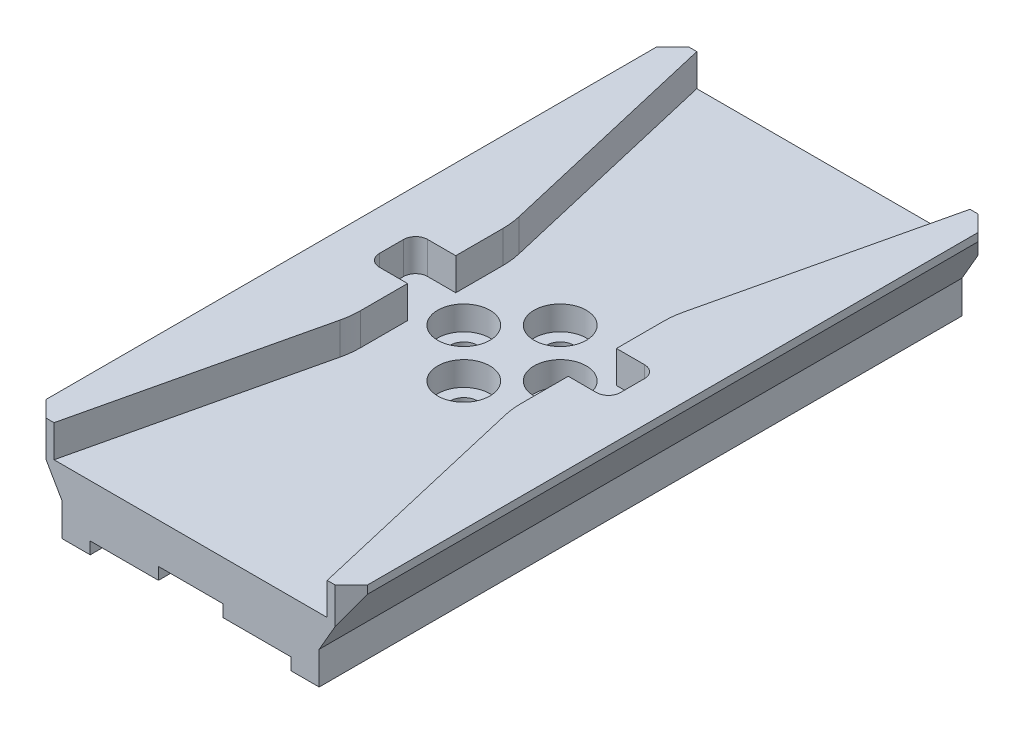
SolidWorks part; units mm, degrees
material "Сплав 2024"
ref_plane "Спереди" through (0, 0, 0) normal (0, 0, 1) x (1, 0, 0)
ref_plane "Сверху" through (0, 0, 0) normal (0, 1, 0) x (1, 0, 0)
ref_plane "Справа" through (0, 0, 0) normal (1, 0, 0) x (0, 0, -1)
sketch "Эскиз1" plane through (0, 0, 0) normal (0, 0, 1) x (1, 0, 0)
  line L0 (-20, 5) -> (-16, -1.9282)
  line L1 (-20, 6) -> (20, 6)
  line L2 (-25.6942, 6) -> (28.5829, 6) construction
  line L3 (-16, -6) -> (16, -6)
  line L4 (0, 6) -> (0, -6) construction
  line L5 (-22.304, 8.9907) -> (-15.6808, -2.4811) construction
  line L7 (-16, -1.9282) -> (-16, -6)
  line L9 (-20, 6) -> (-20, 5)
  line L10 (16, -1.9282) -> (16, -6)
  line L11 (20, 5) -> (16, -1.9282)
  line L12 (20, 6) -> (20, 5)
  point P15 (-20.5774, 6)
  dimension "D1" = 16
  dimension "D2" = 12
  dimension "D3" = 60
  dimension "D4" = 20.5774
  dimension "D6" = 20
  dimension "D7" = 1
extrude "Бобышка-Вытянуть1" add sketch "Эскиз1" along normal blind 80
sketch "Эскиз2" plane through (0, 6, 0) normal (0, 1, 0) x (1, 0, 0)
  line L0 (0, 0) -> (0, -80) construction
  line L1 (20, 0) -> (-20, 0) construction
  line L2 (20, -80) -> (-20, -80) construction
  line L3 (-17, 0) -> (-17, -80) construction
  line L4 (10, -50) -> (17, -80)
  line L5 (-17, 0) -> (-10, -30)
  line L6 (-10, -30) -> (-10, -50)
  line L7 (-10, -50) -> (-17, -80)
  line L8 (10, -30) -> (10, -50)
  line L9 (17, 0) -> (10, -30)
  line L10 (20, -40) -> (-20, -40) construction
  line L11 (-17, 0) -> (17, 0)
  line L12 (17, -80) -> (-17, -80)
  line L20 (-20, -80) -> (-20, 0) construction
  line L21 (20, -80) -> (20, 0) construction
  point P24 (-10, -40)
  dimension "D1" = 10
  dimension "D2" = 3
  dimension "D3" = 20
extrude "Вырез-Вытянуть1" cut sketch "Эскиз2" against normal blind 4
sketch "Эскиз3" plane through (0, 6, 0) normal (0, 1, 0) x (1, 0, 0)
  line L0 (20, -40) -> (-20, -40) construction
  line L4 (-10, -37) -> (-15, -37)
  line L5 (-10, -37) -> (-10, -43)
  line L6 (-10, -43) -> (-15, -43)
  line L7 (-15, -37) -> (-15, -43)
  line L8 (0, 0) -> (0, -80) construction
  line L9 (17, 0) -> (-17, 0) construction
  line L10 (-17, -80) -> (17, -80) construction
  line L11 (10, -37) -> (10, -43)
  line L12 (10, -43) -> (15, -43)
  line L13 (15, -37) -> (15, -43)
  line L14 (10, -37) -> (15, -37)
  line L15 (-10, -30) -> (-10, -50) construction
  line L16 (20, -80) -> (20, 0) construction
  line L17 (-20, -80) -> (-20, 0) construction
  point P12 (-10, -40)
  dimension "D1" = 6
  dimension "D2" = 5
extrude "Вырез-Вытянуть2" cut sketch "Эскиз3" against normal blind 4
fillet "Скругление1" [suppressed] radius 1.5
fillet "Скругление2" radius 10 4 edges at (10, 4, 50) (10, 4, 30) (-10, 4, 30) (-10, 4, 50)
sketch "Эскиз4" plane through (0, 2, 0) normal (0, 1, 0) x (1, 0, 0)
  line L0 (0, 0) -> (0, -80) construction
  line L1 (-17, -80) -> (17, -80) construction
  line L2 (20, -40) -> (-20, -40) construction
  line L5 (20, -80) -> (20, 0) construction
  line L6 (-20, -80) -> (-20, 0) construction
  circle A0 centre (0, -40) radius 6 construction
  dimension "D1" = 12
hole_wizard "Цековка для винта с внутренним шестигранником M31" positions "Эскиз6" profile "Эскиз5" counterbore size "M3" standard "Ansi Metric" end condition through all
sketch "Эскиз6" plane through (0, 2, 0) normal (0, 1, 0) x (1, 0, 0)
  line L0 (0, 0) -> (0, -80) construction
  line L1 (20, -40) -> (-20, -40) construction
  circle A0 centre (0, -40) radius 6 construction
  point P0 (0, -34)
  point P2 (6, -40)
  point P4 (0, -46)
  point P6 (-6, -40)
sketch "Эскиз5" plane through (0, 2, 34) normal (1, 0, 0) x (0, 0, 1)
  line L0 (0, 0) -> (0, 8)
  line L1 (0, 8) -> (1.7, 8)
  line L3 (1.7, 8) -> (1.7, 3)
  line L4 (1.7, 3) -> (3.25, 3)
  line L5 (3.25, 3) -> (3.25, 0)
  line L7 (3.25, 0) -> (0, 0)
  line L11 (0, -6.35) -> (0, 107.95) construction
  dimension "Диаметр сквозного отверстия" = 3.4
  dimension "Глубина сквозного отверстия" = 8
  dimension "Диаметр цековки" = 6.5
  dimension "Глубина цековки" = 3
sketch "Эскиз7" plane through (0, -6, 0) normal (0, -1, 0) x (1, 0, 0)
  line L0 (0, 80) -> (0, 0) construction
  line L2 (-11.5, 77) -> (11.5, 77)
  line L3 (-11.5, 77) -> (-11.5, 51)
  line L5 (-16, 80) -> (16, 80) construction
  line L6 (11.5, 77) -> (11.5, 51)
  line L7 (-11.5, 77) -> (11.5, 51) construction
  line L8 (-11.5, 51) -> (11.5, 77) construction
  arc A0 (-11.5, 51) -> (11.5, 51) centre (0, 19) cw
  point P0 (0, 64)
  dimension "D2" = 26
  dimension "D5" = 45
  dimension "D1" = 3
  dimension "D3" = 23
  dimension "D4" = 26
extrude "Вырез-Вытянуть3" cut sketch "Эскиз7" against normal blind 7
sketch "Эскиз8" plane through (0, 1, 0) normal (0, -1, 0) x (1, 0, 0)
  line L0 (0, 80) -> (0, 0) construction
  line L1 (-16, 80) -> (16, 80) construction
  line L2 (-16, 61.2) -> (16, 61.2) construction
  line L3 (-16, 80) -> (-16, 0) construction
  line L4 (16, 80) -> (16, 0) construction
  line L6 (13.1, 58.95) -> (7.1, 63.45) construction
  line L7 (-13.1, 63.45) -> (-7.1, 63.45)
  line L8 (-13.1, 63.45) -> (-13.1, 58.95)
  line L9 (-13.1, 58.95) -> (-7.1, 58.95)
  line L10 (13.1, 63.45) -> (7.1, 58.95) construction
  line L11 (-13.1, 63.45) -> (-7.1, 58.95) construction
  line L12 (-13.1, 58.95) -> (-7.1, 63.45) construction
  line L13 (13.1, 58.95) -> (7.1, 58.95)
  line L14 (13.1, 63.45) -> (13.1, 58.95)
  line L15 (13.1, 63.45) -> (7.1, 63.45)
  arc A0 (-7.1, 58.95) -> (-7.1, 63.45) centre (-7.1, 61.2) ccw
  arc A1 (7.1, 58.95) -> (7.1, 63.45) centre (7.1, 61.2) cw
  point P17 (-10.1, 61.2)
  point P24 (10.1, 61.2)
  dimension "D1" = 7.1
  dimension "D2" = 4.5
  dimension "D3" = 10.2
  dimension "D4" = 3
extrude "Бобышка-Вытянуть2" add sketch "Эскиз8" along normal blind 3
hole_wizard "Отверстие обработанное метчиком M2.5x0.451" positions "Эскиз10" profile "Эскиз9" tap size "M2.5x0.45" standard "Ansi Metric"
sketch "Эскиз10" plane through (0, -2, 0) normal (0, -1, 0) x (-1, 0, 0)
  point P0 (7.1, -61.2)
  point P2 (-7.1, -61.2)
sketch "Эскиз9" plane through (-7.1, -2, 61.2) normal (1, 0, 0) x (0, 0, -1)
  line L0 (0, 0) -> (0, 3.6159)
  line L1 (0, 3.6159) -> (1.025, 3)
  line L2 (1.025, 3) -> (1.025, 0)
  line L5 (1.025, 0) -> (0, 0)
  line L10 (0, 3.6159) -> (-1.025, 3) construction
  line L11 (0, -6.35) -> (0, 107.95) construction
  dimension "Диаметр сверла" = 2.05
  dimension "Глубина сверла" = 3
  dimension "Угол заточки сверла" = 118
cosmetic thread "Отверстие резьбы7" parameters "D1"=3, "D2"=2.5
cosmetic thread "Отверстие резьбы8" parameters "D1"=3, "D2"=2.5
sketch "Эскиз12" plane through (0, 1, 0) normal (0, -1, 0) x (1, 0, 0)
  line L0 (0, 77) -> (0, 51) construction
  line L1 (11.5, 77) -> (-11.5, 77) construction
  line L2 (-11.5, 51) -> (11.5, 51) construction
  line L3 (-1.8247, 64) -> (1.8247, 64) construction
  line L4 (-13.6614, 76) -> (7.1704, 76) construction
  line L5 (-11.5, 80.8402) -> (-11.5, 69.1924) construction
  line L6 (-11.5, 77) -> (-11.5, 51) construction
  circle A0 centre (-11.5, 76) radius 2
  circle A3 centre (11.5, 76) radius 2
  circle A4 centre (11.5, 52) radius 2
  circle A6 centre (-11.5, 52) radius 2
  point P14 (0, 64)
  dimension "D3" = 4
  dimension "D2" = 1
sketch "Эскиз15" plane through (0, 1, 0) normal (0, -1, 0) x (1, 0, 0)
  line L0 (0, 77) -> (0, 51) construction
  line L1 (11.5, 77) -> (-11.5, 77) construction
  line L2 (-13.8501, 64) -> (13.8501, 64) construction
  line L4 (-11.5, 51) -> (11.5, 51) construction
  line L5 (11.5, 51) -> (11.5, 77) construction
  line L7 (11.5, 77) -> (-11.5, 77) construction
  line L8 (-11.5, 77) -> (-11.5, 63.45) construction
  line L9 (-11.5, 77) -> (-11.5, 51) construction
  circle A0 centre (-11.5, 51) radius 2.5
  circle A1 centre (11.5, 51) radius 2.5
  circle A2 centre (-9, 77) radius 2.5
  circle A3 centre (9, 77) radius 2.5
  point P8 (0, 64)
  dimension "D1" = 5
  dimension "D2" = 5
  dimension "D3" = 5
extrude "Бобышка-Вытянуть5" add sketch "Эскиз15" along normal up to surface (7 mm away) up to face at (0, -6, 64.5009)
fillet "Скругление8" radius 3 12 edges at (11.5, -2.5, 53.5) (9.1178, -2.5, 51.7584) (-9.1178, -2.5, 51.7584) (-11.5, -2.5, 53.5) (-11.5, -0.5, 58.95) (11.5, -0.5, 58.95) (11.5, -0.5, 63.45) (-11.5, -0.5, 63.45) (-11.5, -2.5, 77) (11.5, -2.5, 77) (6.5, -2.5, 77) (-6.5, -2.5, 77)
sketch "Эскиз16" plane through (0, -6, 0) normal (0, -1, 0) x (1, 0, 0)
  line L0 (-16, 80) -> (16, 80) construction
  line L1 (-12.5, 80) -> (12.5, 80)
  line L70 (-12.5, 54.3541) -> (-12.5, 80)
  line L71 (12.5, 54.3541) -> (12.5, 80)
  line L72 (-11.5, 71.5228) -> (-11.5, 55.6098) construction
  line L73 (11.5, 55.6098) -> (11.5, 71.5228) construction
  arc A0 (7.2531, 52.2211) -> (-7.2531, 52.2211) centre (0, 19) ccw construction
  arc A1 (7.2531, 52.2211) -> (-7.2531, 52.2211) centre (0, 19) ccw construction
  arc A2 (8.0001, 51.0194) -> (-8.0001, 51.0194) centre (0, 19) ccw
  arc A3 (7.0398, 51.2441) -> (-7.0398, 51.2441) centre (0, 19) ccw construction
  arc A42 (-12.5, 54.3541) -> (-8.0001, 51.0194) centre (-11.5, 51) ccw
  arc A43 (8.0001, 51.0194) -> (12.5, 54.3541) centre (11.5, 51) ccw
  dimension "D3" = 7
  dimension "D4" = 7
  dimension "D6" = 1
  dimension "D7" = 1
  dimension "D2" = 1
extrude "Вырез-Вытянуть6" cut sketch "Эскиз16" against normal blind 1.5
fillet "Скругление9" radius 3 4 edges at (12.5, -5.25, 54.3541) (8.0001, -5.25, 51.0194) (-8.0001, -5.25, 51.0194) (-12.5, -5.25, 54.3541)
hole_wizard "Отверстие обработанное метчиком M3x0.52" positions "Эскиз19" profile "Эскиз18" tap size "M3x0.5" standard "Ansi Metric"
sketch "Эскиз19" plane through (0, -4.5, 0) normal (0, -1, 0) x (-1, 0, 0)
  point P0 (11.5, -51)
  point P3 (-11.5, -51)
  point P6 (-9, -77)
  point P9 (9, -77)
sketch "Эскиз18" plane through (-11.5, -4.5, 51) normal (1, 0, 0) x (0, 0, -1)
  line L0 (0, 0) -> (0, 6.2501)
  line L1 (0, 6.2501) -> (1.25, 5.499)
  line L2 (1.25, 5.499) -> (1.25, 0)
  line L5 (1.25, 0) -> (0, 0)
  line L10 (0, 6.2501) -> (-1.25, 5.499) construction
  line L11 (0, -6.35) -> (0, 107.95) construction
  dimension "Диаметр сверла" = 2.5
  dimension "Глубина сверла" = 5.499
  dimension "Угол заточки сверла" = 118
cosmetic thread "Отверстие резьбы9" parameters "D1"=5.5, "D2"=3
cosmetic thread "Отверстие резьбы10" parameters "D1"=5.5, "D2"=3
cosmetic thread "Отверстие резьбы11" parameters "D1"=5.5, "D2"=3
cosmetic thread "Отверстие резьбы12" parameters "D1"=5.5, "D2"=3
sketch "Эскиз20" plane through (0, -4.5, 0) normal (0, -1, 0) x (1, 0, 0)
  line L0 (0, 80) -> (0, 67.2176) construction
  line L1 (12.5, 80) -> (-12.5, 80) construction
  line L2 (-4.3902, 77) -> (4.3902, 77) construction
  line L3 (-4, 80) -> (4, 80)
  line L4 (-4, 80) -> (-4, 77)
  line L5 (-4, 77) -> (4, 77)
  line L6 (4, 80) -> (4, 77)
  line L7 (-4, 80) -> (4, 77) construction
  line L8 (-4, 77) -> (4, 80) construction
  point P5 (0, 78.5)
  dimension "D1" = 8
extrude "Вырез-Вытянуть7" cut sketch "Эскиз20" against normal blind 1.5
sketch "Эскиз21" plane through (0, -2, 0) normal (0, -1, 0) x (1, 0, 0)
  line L0 (11.5, 61.2) -> (-11.5, 61.2) construction
  line L1 (11.5, 55.95) -> (11.5, 66.45) construction
  line L2 (-11.5, 55.95) -> (-11.5, 66.45) construction
  line L3 (0, 53.0037) -> (0, 77) construction
  line L4 (4.3902, 77) -> (-4.3902, 77) construction
  line L6 (-5.5, 63.7) -> (5.5, 63.7)
  line L7 (-5.5, 63.7) -> (-5.5, 58.7)
  line L8 (-5.5, 58.7) -> (5.5, 58.7)
  line L9 (5.5, 63.7) -> (5.5, 58.7)
  line L10 (-5.5, 63.7) -> (5.5, 58.7) construction
  line L11 (-5.5, 58.7) -> (5.5, 63.7) construction
  arc A0 (7.2531, 52.2211) -> (-7.2531, 52.2211) centre (0, 19) ccw construction
  point P13 (0, 61.2)
  dimension "D1" = 11
  dimension "D2" = 5
extrude "Вырез-Вытянуть8" cut sketch "Эскиз21" against normal up to surface (3 mm away) up to face at (0, 1, 62.8736)
ref_plane "Плоскость1" through (0, 0, 40) normal (0, 0, 1) x (1, 0, 0)
mirror "Зеркальное отражение1" about plane through (0, 0, 40) normal (0, 0, 1) of "Вырез-Вытянуть3"
fillet "Скругление10" radius 3 4 edges at (11.5, -2.5, 3) (-11.5, -2.5, 3) (-11.5, -2.5, 29) (11.5, -2.5, 29)
sketch "Эскиз23" plane through (0, 6, 0) normal (0, 1, 0) x (1, 0, 0)
  line L0 (-17, 0) -> (-20, 0) construction
  line L1 (-20, -80) -> (-20, 0) construction
  line L2 (-17.464, 0) -> (-20, 0)
  line L3 (-20, 0) -> (-20, -2.536)
  line L4 (0, 0) -> (0, -80) construction
  line L5 (-17, -80) -> (17, -80) construction
  line L6 (20, -40) -> (-20, -40) construction
  line L7 (20, -80) -> (20, 0) construction
  line L8 (20, 0) -> (20, -2.536)
  line L9 (17.464, 0) -> (20, 0)
  line L10 (20, -2.536) -> (17.464, 0)
  line L11 (20, -77.464) -> (17.464, -80)
  line L12 (17.464, -80) -> (20, -80)
  line L13 (20, -80) -> (20, -77.464)
  line L14 (-20, -2.536) -> (-17.464, 0)
  line L15 (-20, -77.464) -> (-17.464, -80)
  line L16 (-20, -80) -> (-20, -77.464)
  line L17 (-17.464, -80) -> (-20, -80)
  dimension "D1" = 45
extrude "Вырез-Вытянуть10" [suppressed] cut sketch "Эскиз23" against normal through all
fillet "Скругление14" radius 1.5 4 edges at (-15, 4, 37) (-15, 4, 43) (15, 4, 37) (15, 4, 43)
chamfer "Фаска1" distance 2 angle 45 4 edges at (-20, 5.5, 80) (20, 5.5, 80) (20, 5.5, 0) (-20, 5.5, 0)
